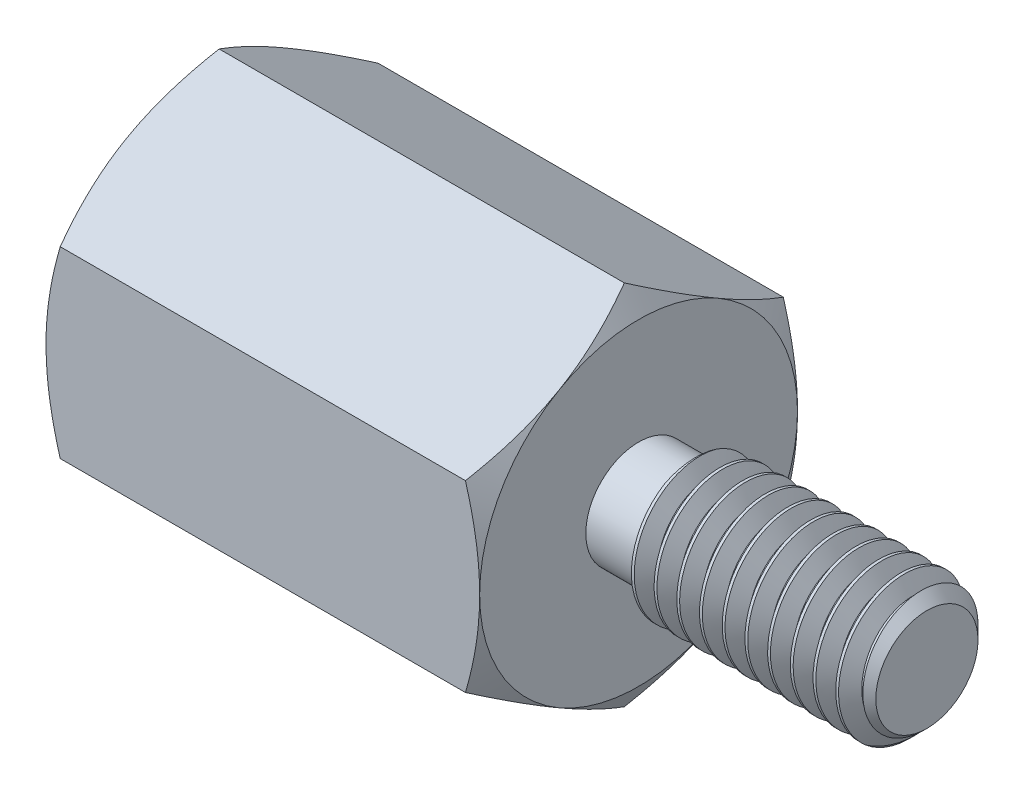
SolidWorks part; units mm, degrees
ref_plane "Front Plane" through (0, 0, 0) normal (0, 0, 1) x (1, 0, 0)
ref_plane "Top Plane" through (0, 0, 0) normal (0, 1, 0) x (1, 0, 0)
ref_plane "Right Plane" through (0, 0, 0) normal (1, 0, 0) x (0, 0, -1)
sketch "Sketch1" plane through (0, 0, 0) normal (0, 0, 1) x (1, 0, 0)
  line L0 (0, 0) -> (31.8, 0) construction
  line L1 (19.1, 7) -> (19.1, -7) construction
  line L2 (31.8, 3) -> (31.8, -3) construction
  line L3 (0, 4) -> (0, -4) construction
  line L4 (31.8, -3) -> (19.1, -3) construction
  point P7 (9.5, 0)
  point P8 (19.1, 0)
  point P11 (24.1, -3)
  dimension "D1" = 5
  dimension "A" = 19.1
  dimension "Hex" = 14
  dimension "Female Thread Length" = 9.5
  dimension "Male thread Length" = 12.7
  dimension "Male Dia" = 6
  dimension "Female Dia" = 8
ref_plane "Plane1" through (19.1, 0, 0) normal (1, 0, 0) x (0, 0, -1)
sketch "Sketch2" plane through (19.1, 0, 0) normal (1, 0, 0) x (0, 0, -1)
  line L1 (0, 8.0829) -> (-7, 4.0415)
  line L2 (-7, 4.0415) -> (-7, -4.0415)
  line L3 (-7, -4.0415) -> (0, -8.0829)
  line L4 (0, -8.0829) -> (7, -4.0415)
  line L5 (7, -4.0415) -> (7, 4.0415)
  line L6 (7, 4.0415) -> (0, 8.0829)
  circle A0 centre (0, 0) radius 7 construction
extrude "Extrude1" add sketch "Sketch2" against normal up to vertex (19.1 mm away) up to point (0, 0, 0)
sketch "Sketch3" plane through (0, 0, 0) normal (-1, 0, 0) x (0, 0, 1)
  circle A0 centre (0, 0) radius 4
extrude "Extrude3" cut sketch "Sketch3" against normal up to vertex (9.5 mm away) up to point (9.5, 0, 0)
sketch "Sketch8" plane through (9.5, 0, 0) normal (-1, 0, 0) x (0, 0, 1)
  circle A1 centre (0, 0) radius 4
  circle A2 centre (0, 0) radius 4
  dimension "D1" = 0
curve "Helix/Spiral1" pitch 1.25 height 12 turns 9.6 parameters "Female Pitch"=1.25
sketch "Sketch9" plane through (0, 0, 0) normal (0, 0, 1) x (1, 0, 0)
  line L0 (10.0469, 4) -> (8.9531, 4)
  line L1 (10.0469, 4) -> (9.5781, 3.1881)
  line L2 (9.5781, 3.1881) -> (9.4219, 3.1881)
  line L3 (9.4219, 3.1881) -> (8.9531, 4)
  line L4 (9.5, 3.1881) -> (9.5, 4) construction
  line L5 (9.8125, 3.5941) -> (9.1875, 3.5941) construction
  dimension "D1" = 60
  dimension "D2" = 0.1562
  dimension "D3" = 0.625
sweep "Sweep1" add profiles "Sketch9" path "Helix/Spiral1"
sketch "Sketch10" plane through (0, 0, 0) normal (-1, 0, 0) x (0, 0, 1)
  line L6 (0, 8.0829) -> (-7, 4.0415)
  line L7 (-7, 4.0415) -> (-7, -4.0415)
  line L8 (-7, -4.0415) -> (0, -8.0829)
  line L9 (0, -8.0829) -> (7, -4.0415)
  line L10 (7, -4.0415) -> (7, 4.0415)
  line L11 (7, 4.0415) -> (0, 8.0829)
  line L12 (0, 8.0829) -> (-7, 4.0415)
  line L13 (-7, 4.0415) -> (-7, -4.0415)
  line L14 (-7, -4.0415) -> (0, -8.0829)
  line L15 (0, -8.0829) -> (7, -4.0415)
  line L16 (7, -4.0415) -> (7, 4.0415)
  line L17 (7, 4.0415) -> (0, 8.0829)
  dimension "D1" = 0
extrude "Extrude7" cut sketch "Sketch10" along normal through all
sketch "Sketch11" plane through (0, 0, 0) normal (-1, 0, 0) x (0, 0, 1)
  circle A2 centre (0, 0) radius 4.0762
  circle A3 centre (0, 0) radius 4.0762
  dimension "D1" = 0.0762
extrude "Extrude8" cut sketch "Sketch11" against normal through all draft 45
sketch "Sketch6" plane through (19.1, 0, 0) normal (1, 0, 0) x (0, 0, -1)
  circle A0 centre (0, 0) radius 7 construction
  circle A1 centre (0, 0) radius 7
extrude "Extrude5" cut sketch "Sketch6" against normal through all draft 60 flip side to cut
sketch "Sketch7" plane through (0, 0, 0) normal (-1, 0, 0) x (0, 0, 1)
  circle A1 centre (0, 0) radius 7
  circle A2 centre (0, 0) radius 7
  dimension "D1" = 0
extrude "Extrude6" cut sketch "Sketch7" against normal through all draft 60 flip side to cut
ref_plane "Plane2" through (31.8, 0, 0) normal (1, 0, 0) x (0, 0, -1)
sketch "Sketch4" plane through (31.8, 0, 0) normal (1, 0, 0) x (0, 0, -1)
  circle A0 centre (0, 0) radius 3
extrude "Extrude4" add sketch "Sketch4" against normal up to vertex (12.7 mm away) separate body up to point (19.1, 0, 0)
sketch "Sketch12" plane through (19.1, 0, 0) normal (-1, 0, 0) x (0, 0, 1)
  circle A1 centre (0, 0) radius 3
  circle A2 centre (0, 0) radius 3
  dimension "D1" = 0
curve "Helix/Spiral2" pitch 1 height 14.7 turns 14.7 parameters "Male Pitch"=1
sketch "Sketch13" plane through (0, 0, 0) normal (0, 0, 1) x (1, 0, 0)
  line L0 (18.6625, 3) -> (19.0375, 2.3505)
  line L1 (19.0375, 2.3505) -> (19.1625, 2.3505)
  line L2 (19.1625, 2.3505) -> (19.5375, 3)
  line L3 (18.6625, 3) -> (19.5375, 3)
  line L4 (19.1, 2.3505) -> (19.1, 3) construction
  line L5 (18.85, 2.6752) -> (19.35, 2.6752) construction
  line L6 (19.1, 0) -> (19.1, 6.0622) construction
  line L7 (31.8, 3) -> (19.1, 3) construction
  dimension "D1" = 60
  dimension "D2" = 0.125
  dimension "D3" = 0.5
chamfer "Chamfer1" distance 0.75 angle 45 1 edges at (31.8, 0, -3)
sweep "Cut-Sweep1" cut profiles "Sketch13" path "Helix/Spiral2" align with end faces yes
sketch "Sketch14" plane through (0, 0, 0) normal (0, 0, 1) x (1, 0, 0)
  line L0 (19.1, 3) -> (19.1, 2.3251)
  line L1 (19.1, 2.3251) -> (21.2227, 2.3251)
  line L2 (21.2227, 2.3251) -> (21.6123, 3)
  line L3 (19.1, 3) -> (21.6123, 3)
  line L4 (19.1, 7) -> (19.1, -7) construction
  line L5 (18.6625, 3) -> (19.5375, 3) construction
  dimension "D1" = 60
  dimension "D2" = 2.5123
  dimension "D3" = 0.0254
revolve "Cut-Revolve1" cut sketch "Sketch14" angle 360 about L0
combine bodies "Combine1" operation type add bodies to combine 110 105
sketch "Sketch15" plane through (0, 0, 0) normal (0, 0, 1) x (1, 0, 0)
  line L1 (0, -4) -> (9.5, -4)
  line L2 (0, -4) -> (0, 4)
  line L3 (0, 4) -> (9.5, 4)
  line L4 (9.5, -4) -> (9.5, 4)
equation "\"D3@Helix/Spiral1\" = \"Female Thread Length@Sketch1\"+(\"Female Pitch@Helix/Spiral1\"*2)"
equation "\"D2@Sketch9\" = \"Female Pitch@Helix/Spiral1\"*.125"
equation "\"D3@Sketch9\" = \"Female Pitch@Helix/Spiral1\"*.5"
equation "\"D3@Helix/Spiral2\" = \"Male thread Length@Sketch1\"+(\"Male Pitch@Helix/Spiral2\"*2)"
equation "\"D2@Sketch13\" = \"Male Pitch@Helix/Spiral2\"*.125"
equation "\"D3@Sketch13\" = \"Male Pitch@Helix/Spiral2\"*.5"
equation "\"D1@Chamfer1\" = \"Male Pitch@Helix/Spiral2\"*.750"
equation "\"D2@Sketch14\" = \"Male Pitch@Helix/Spiral2\"*2.5123456"
equation "\"D1@Sketch1\" = \"Male Pitch@Helix/Spiral2\"*5.0"
